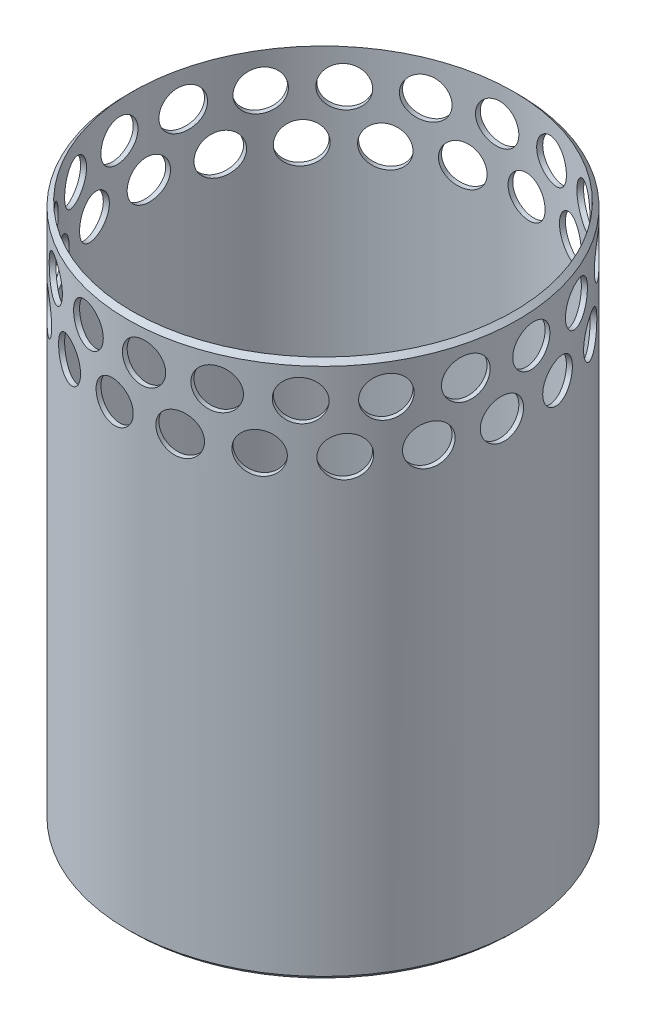
SolidWorks part; units mm, degrees
material "Plain Carbon Steel"
ref_plane "Front Plane" through (0, 0, 0) normal (0, 0, 1) x (1, 0, 0)
ref_plane "Top Plane" through (0, 0, 0) normal (0, 1, 0) x (1, 0, 0)
ref_plane "Right Plane" through (0, 0, 0) normal (1, 0, 0) x (0, 0, -1)
sketch "Sketch1" plane through (0, 0, 0) normal (0, 1, 0) x (1, 0, 0)
  circle A0 centre (0, 0) radius 80.55
  circle A1 centre (0, 0) radius 82.55
  dimension "D1" = 165.1
  dimension "D2" = 2
extrude "Boss-Extrude1" add sketch "Sketch1" along normal blind 227.4
chamfer "Chamfer1" distance 2 angle 45 2 edges at (0, 0, 82.55) (0, 227.4, 82.55)
sketch "Sketch2" plane through (0, 0, 0) normal (0, 0, 1) x (1, 0, 0)
  line L0 (-6.2145, 212.6655) -> (0, 202.4) construction
  line L2 (0, 202.4) -> (6.2145, 192.1345) construction
  line L4 (0, 0) -> (0, 50.3884) construction
  line L5 (80.55, 227.4) -> (-80.55, 227.4) construction
  circle A0 centre (-6.2145, 212.6655) radius 8.5
  circle A1 centre (6.2145, 192.1345) radius 8.5
  point P4 (0, 0)
  point P8 (0, 207.5201)
  dimension "D1" = 17
  dimension "D2" = 12
  dimension "D3" = 25
  dimension "D4" = 31.19
extrude "Cut-Extrude1" cut sketch "Sketch2" against normal through all
ref_axis "Axis1" through (0, 227.4, 0) along (0, -1, 0)
pattern_circular "CirPattern1" count 20 over 360 about axis through (0, 227.4, 0) along (0, -1, 0) of "Cut-Extrude1"
equation "\"TubeDiameter\" = 6.500in"
equation "\"D1@Sketch1\"=\"TubeDiameter\""
